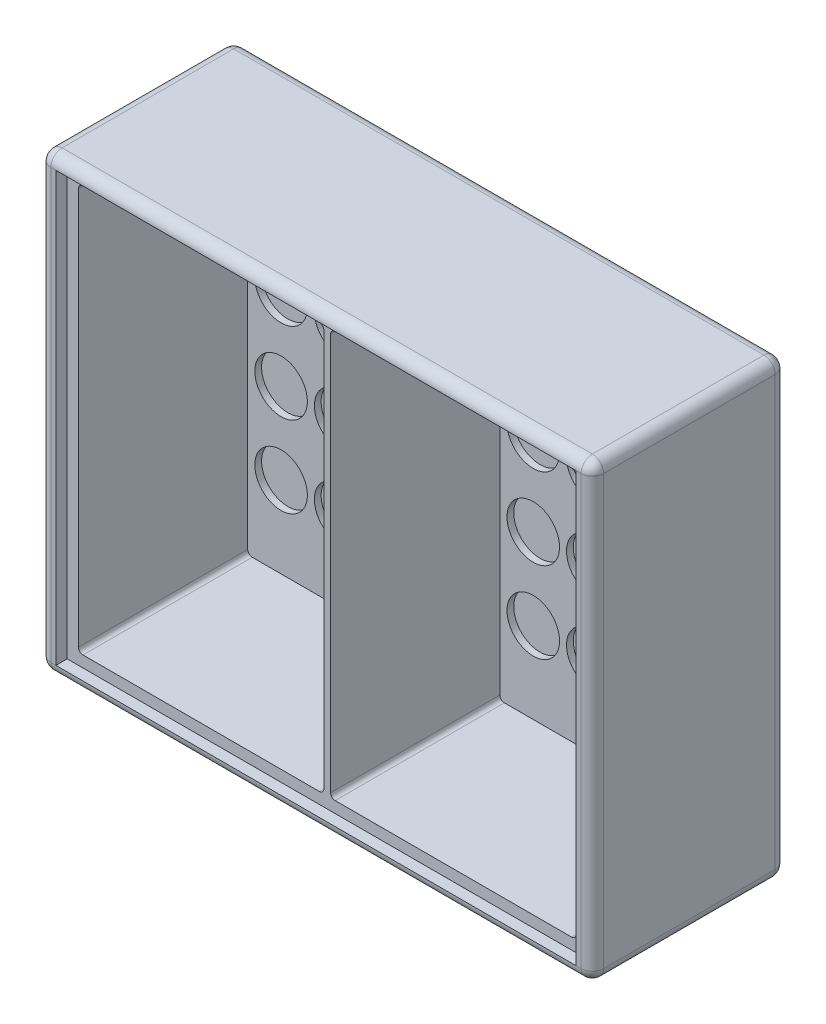
SolidWorks part; units mm, degrees
ref_plane "Front Plane" through (0, 0, 0) normal (0, 0, 1) x (1, 0, 0)
ref_plane "Top Plane" through (0, 0, 0) normal (0, 1, 0) x (1, 0, 0)
ref_plane "Right Plane" through (0, 0, 0) normal (1, 0, 0) x (0, 0, -1)
sketch "Sketch1" plane through (0, 0, 0) normal (0, 0, 1) x (1, 0, 0)
  line L1 (122.5, -100) -> (-122.5, -100)
  line L2 (122.5, -100) -> (122.5, 100)
  line L3 (122.5, 100) -> (-122.5, 100)
  line L4 (-122.5, -100) -> (-122.5, 100)
  line L5 (122.5, -100) -> (-122.5, 100) construction
  line L6 (122.5, 100) -> (-122.5, -100) construction
  point P0 (0, 0)
  dimension "D1" = 200
  dimension "D2" = 245
extrude "Boss-Extrude1" add sketch "Sketch1" along normal blind 6
sketch "Sketch2" plane through (0, 0, 6) normal (0, 0, 1) x (1, 0, 0)
  line L1 (-122.5, -100) -> (122.5, -100)
  line L2 (-122.5, -100) -> (-122.5, 100)
  line L3 (-122.5, 100) -> (122.5, 100)
  line L4 (122.5, -100) -> (122.5, 100)
  line L5 (-122.5, -100) -> (122.5, 100) construction
  line L6 (-122.5, 100) -> (122.5, -100) construction
  line L7 (-110.25, -90) -> (110.25, -90)
  line L8 (-110.25, -90) -> (-110.25, 90)
  line L9 (-110.25, 90) -> (110.25, 90)
  line L10 (110.25, -90) -> (110.25, 90)
  line L11 (-110.25, -90) -> (110.25, 90) construction
  line L12 (-110.25, 90) -> (110.25, -90) construction
  point P0 (0, 0)
  point P7 (0, 0)
  dimension "D1" = 10
extrude "Boss-Extrude2" add sketch "Sketch2" along normal blind 80
sketch "Sketch3" plane through (0, 0, 6) normal (0, 0, 1) x (1, 0, 0)
  line L0 (110.25, 90) -> (-110.25, 90) construction
  line L1 (-1.5, -90) -> (1.5, -90)
  line L2 (-1.5, -90) -> (-1.5, 90)
  line L3 (-1.5, 90) -> (1.5, 90)
  line L4 (1.5, -90) -> (1.5, 90)
  line L5 (-1.5, -90) -> (1.5, 90) construction
  line L6 (-1.5, 90) -> (1.5, -90) construction
  point P0 (0, 0)
  dimension "D1" = 3
extrude "Boss-Extrude3" add sketch "Sketch3" along normal blind 75
sketch "Sketch5" plane through (0, 0, 86) normal (0, 0, 1) x (1, 0, 0)
  line L1 (-110.25, -90) -> (110.25, -90)
  line L2 (-110.25, -90) -> (-110.25, 90)
  line L3 (-110.25, 90) -> (110.25, 90)
  line L4 (110.25, -90) -> (110.25, 90)
  line L5 (-110.25, -90) -> (110.25, 90) construction
  line L6 (-110.25, 90) -> (110.25, -90) construction
  line L7 (-115.25, -95) -> (115.25, -95)
  line L8 (-115.25, -95) -> (-115.25, 95)
  line L9 (-115.25, 95) -> (115.25, 95)
  line L10 (115.25, -95) -> (115.25, 95)
  line L11 (-115.25, -95) -> (115.25, 95) construction
  line L12 (-115.25, 95) -> (115.25, -95) construction
  point P0 (0, 0)
  point P7 (0, 0)
  dimension "D1" = 5
  dimension "D2" = 5
extrude "Cut-Extrude1" cut sketch "Sketch5" against normal up to surface (5 mm away) up to face at (0, 0, 81)
sketch "Sketch6" plane through (0, 0, 6) normal (0, 0, 1) x (1, 0, 0)
  line L0 (0, 95) -> (0, -95) construction
  line L1 (115.25, 95) -> (-115.25, 95) construction
  line L2 (-115.25, -95) -> (115.25, -95) construction
  line L3 (42.68, 100) -> (42.68, -100) construction
  line L4 (69.07, 100) -> (69.07, -100) construction
  line L5 (16.29, 100) -> (16.29, -100) construction
  line L6 (122.5, 100) -> (-122.5, 100) construction
  line L7 (-122.5, -100) -> (122.5, -100) construction
  line L8 (1.5, 54) -> (110.25, 54) construction
  line L9 (110.25, -90) -> (110.25, 90) construction
  line L10 (110.25, 90) -> (1.5, 90) construction
  line L11 (1.5, -90) -> (1.5, 90) construction
  line L12 (95.46, 100) -> (95.46, -100) construction
  line L13 (1.5, -90) -> (1.5, 90) construction
  line L14 (16.29, 100) -> (42.68, 100) construction
  line L15 (1.5, 18) -> (110.25, 18) construction
  line L16 (1.5, -18) -> (110.25, -18) construction
  line L17 (1.5, -54) -> (110.25, -54) construction
  line L18 (1.5, 54) -> (1.5, 18) construction
  line L19 (16.29, 54) -> (16.29, 18) construction
  circle A4 centre (16.29, 54) radius 11.65
  circle A5 centre (42.68, 54) radius 11.65
  circle A6 centre (69.07, 54) radius 11.65
  circle A7 centre (95.46, 54) radius 11.65
  circle A8 centre (16.29, 18) radius 11.65
  circle A9 centre (42.68, 18) radius 11.65
  circle A10 centre (69.07, 18) radius 11.65
  circle A11 centre (95.46, 18) radius 11.65
  circle A12 centre (16.29, -18) radius 11.65
  circle A13 centre (42.68, -18) radius 11.65
  circle A14 centre (69.07, -18) radius 11.65
  circle A15 centre (95.46, -18) radius 11.65
  circle A16 centre (16.29, -54) radius 11.65
  circle A17 centre (42.68, -54) radius 11.65
  circle A18 centre (69.07, -54) radius 11.65
  circle A19 centre (95.46, -54) radius 11.65
  circle A20 centre (-95.46, -54) radius 11.65
  circle A21 centre (-69.07, -54) radius 11.65
  circle A22 centre (-42.68, -54) radius 11.65
  circle A23 centre (-16.29, -54) radius 11.65
  circle A24 centre (-95.46, -18) radius 11.65
  circle A25 centre (-69.07, -18) radius 11.65
  circle A26 centre (-42.68, -18) radius 11.65
  circle A27 centre (-16.29, -18) radius 11.65
  circle A28 centre (-95.46, 18) radius 11.65
  circle A29 centre (-69.07, 18) radius 11.65
  circle A30 centre (-42.68, 18) radius 11.65
  circle A31 centre (-16.29, 18) radius 11.65
  circle A32 centre (-95.46, 54) radius 11.65
  circle A33 centre (-69.07, 54) radius 11.65
  circle A34 centre (-42.68, 54) radius 11.65
  circle A35 centre (-16.29, 54) radius 11.65
  point P46 (16.29, 54)
  dimension "D7" = 23.3
  dimension "D1" = 14.79
  dimension "D2" = 4
  dimension "D3" = 26.39
  dimension "D4" = 36
  dimension "D5" = 36
  dimension "D8" = 36
  dimension "D6" = 4
  dimension "D9" = 4
extrude "Cut-Extrude2" cut sketch "Sketch6" against normal blind 3
fillet "Fillet1" radius 5 12 edges at (122.5, 0, 86) (122.5, 0, 0) (122.5, 100, 43) (0, 100, 86) (0, 100, 0) (-122.5, 100, 43) (-122.5, 0, 86) (-122.5, 0, 0) (-122.5, -100, 43) (0, -100, 86) (122.5, -100, 43) (0, -100, 0)
fillet "Fillet2" radius 2 8 edges at (1.5, -90, 43.5) (-1.5, -90, 43.5) (-1.5, 90, 43.5) (1.5, 90, 43.5) (-110.25, -90, 43.5) (-110.25, 90, 43.5) (110.25, -90, 43.5) (110.25, 90, 43.5)
